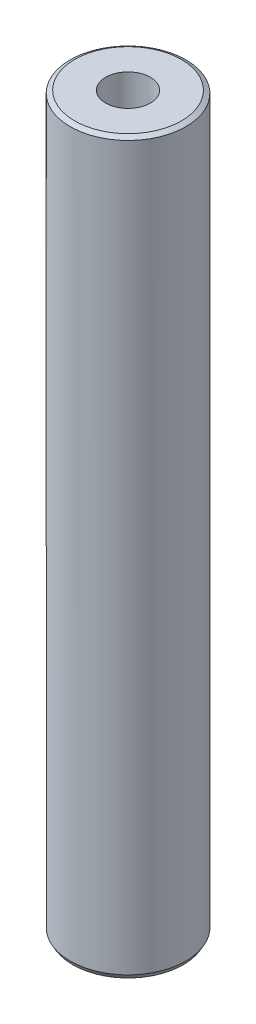
SolidWorks part; units mm, degrees
ref_plane "Front Plane" through (0, 0, 0) normal (0, 0, 1) x (1, 0, 0)
ref_plane "Top Plane" through (0, 0, 0) normal (0, 1, 0) x (1, 0, 0)
ref_plane "Right Plane" through (0, 0, 0) normal (1, 0, 0) x (0, 0, -1)
sketch "Sketch1" plane through (0, 0, 0) normal (0, 1, 0) x (1, 0, 0)
  circle A0 centre (0, 0) radius 35
  dimension "SHAFT_OD" = 70
extrude "Boss-Extrude1" add sketch "Sketch1" along normal blind 441.2398
sketch "Sketch2" plane through (0, 0, 0) normal (0, 1, 0) x (1, 0, 0)
  circle A0 centre (0, 0) radius 13.5408
  dimension "BORE_D" = 27.0816
extrude "Cut-Extrude1" cut sketch "Sketch2" along normal through all
chamfer "Chamfer1" distance 1.5976 angle 60 2 edges at (0, 441.2398, 35) (0, 0, 35) first distance on face at (0, 441.2398, 35) first distance on face at (0, 0, 13.5408)
